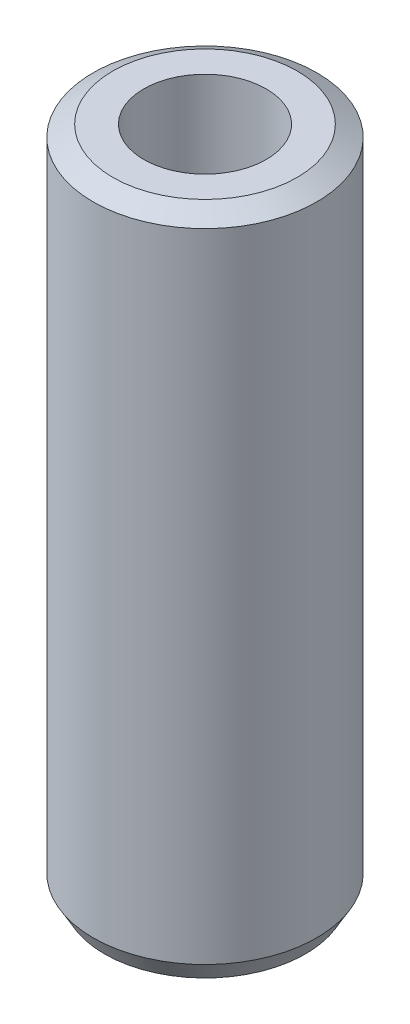
SolidWorks part; units mm, degrees
ref_plane "Front Plane" through (0, 0, 0) normal (0, 0, 1) x (1, 0, 0)
ref_plane "Top Plane" through (0, 0, 0) normal (0, 1, 0) x (1, 0, 0)
ref_plane "Right Plane" through (0, 0, 0) normal (1, 0, 0) x (0, 0, -1)
sketch "Sketch1" plane through (0, 0, 0) normal (0, 1, 0) x (1, 0, 0)
  circle A0 centre (0, 0) radius 57.5
  dimension "SHAFT_OD" = 115
extrude "Boss-Extrude1" add sketch "Sketch1" along normal blind 343.5423
sketch "Sketch2" plane through (0, 0, 0) normal (0, 1, 0) x (1, 0, 0)
  circle A0 centre (0, 0) radius 31.4744
  dimension "BORE_D" = 62.9488
extrude "Cut-Extrude1" cut sketch "Sketch2" along normal through all
chamfer "Chamfer1" distance 5.8378 angle 60 2 edges at (0, 343.5423, 57.5) (0, 0, 57.5) first distance on face at (0, 343.5423, 57.5) first distance on face at (0, 0, 31.4744)
